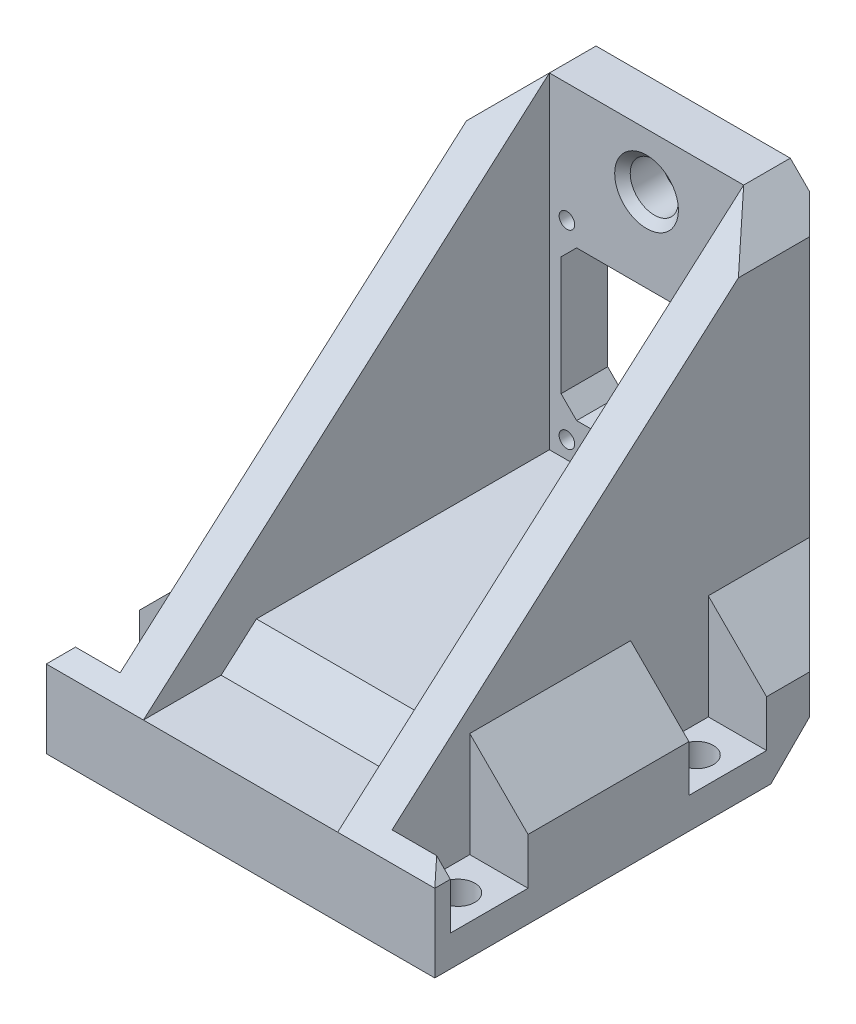
SolidWorks part; units mm, degrees
ref_plane "Front Plane" through (0, 0, 0) normal (0, 0, 1) x (1, 0, 0)
ref_plane "Top Plane" through (0, 0, 0) normal (0, 1, 0) x (1, 0, 0)
ref_plane "Right Plane" through (0, 0, 0) normal (1, 0, 0) x (0, 0, -1)
sketch "Sketch1" plane through (0, 0, 0) normal (0, 1, 0) x (1, 0, 0)
  line L1 (-25, 29.125) -> (25, 29.125)
  line L2 (-25, 29.125) -> (-25, -29.125)
  line L3 (-25, -29.125) -> (25, -29.125)
  line L4 (25, 29.125) -> (25, -29.125)
  line L5 (-25, 29.125) -> (25, -29.125) construction
  line L6 (-25, -29.125) -> (25, 29.125) construction
  point P0 (0, 0)
  dimension "D1" = 50
  dimension "D2" = 58.25
extrude "Boss-Extrude1" add sketch "Sketch1" along normal blind 10
sketch "Sketch2" plane through (0, 0, 0) normal (0, 1, 0) x (1, 0, 0)
  line L0 (-25, -29.125) -> (25, -29.125) construction
  line L1 (-21, -22.125) -> (21, -22.125) construction
  line L2 (-21, -22.125) -> (-21, 8.575) construction
  line L3 (-21, 8.575) -> (21, 8.575) construction
  line L4 (21, -22.125) -> (21, 8.575) construction
  line L5 (-21, -22.125) -> (21, 8.575) construction
  line L6 (-21, 8.575) -> (21, -22.125) construction
  circle A0 centre (-21, 8.575) radius 2.15
  circle A1 centre (-21, -22.125) radius 2.15
  circle A2 centre (21, 8.575) radius 2.15
  circle A3 centre (21, -22.125) radius 2.15
  point P0 (0, -6.775)
  dimension "D4" = 4.3
  dimension "D1" = 42
  dimension "D2" = 30.7
  dimension "D3" = 7
extrude "Cut-Extrude1" cut sketch "Sketch2" along normal blind 4
sketch "Sketch5" plane through (0, 10, 0) normal (0, 1, 0) x (1, 0, 0)
  line L0 (25, 29.125) -> (-25, 29.125) construction
  line L1 (-12.5, 23.125) -> (12.5, 23.125)
  line L2 (-12.5, 23.125) -> (-12.5, 29.125)
  line L3 (-12.5, 29.125) -> (12.5, 29.125)
  line L4 (12.5, 23.125) -> (12.5, 29.125)
  line L5 (-12.5, 23.125) -> (12.5, 29.125) construction
  line L6 (-12.5, 29.125) -> (12.5, 23.125) construction
  point P0 (0, 26.125)
  dimension "D1" = 6
  dimension "D2" = 25
extrude "Boss-Extrude3" add sketch "Sketch5" along normal blind 46
sketch "Sketch6" plane through (0, 0, -29.125) normal (0, 0, -1) x (-1, 0, 0)
  line L1 (-11, 19) -> (11, 19)
  line L2 (-11, 19) -> (-11, 38.25)
  line L3 (-11, 38.25) -> (11, 38.25)
  line L4 (11, 19) -> (11, 38.25)
  line L5 (-11, 19) -> (11, 38.25) construction
  line L6 (-11, 38.25) -> (11, 19) construction
  line L7 (-12.5, 56) -> (12.5, 56) construction
  point P0 (0, 28.625)
  dimension "D1" = 22
  dimension "D2" = 19.25
  dimension "D3" = 17.75
extrude "Cut-Extrude3" cut sketch "Sketch6" against normal up to next
sketch "Sketch7" plane through (0, 0, -23.125) normal (0, 0, 1) x (1, 0, 0)
  line L1 (-10.25, 16.25) -> (10.25, 16.25) construction
  line L2 (-10.25, 16.25) -> (-10.25, 40.7) construction
  line L3 (-10.25, 40.7) -> (10.25, 40.7) construction
  line L4 (10.25, 16.25) -> (10.25, 40.7) construction
  line L5 (-10.25, 16.25) -> (10.25, 40.7) construction
  line L6 (-10.25, 40.7) -> (10.25, 16.25) construction
  line L7 (-12.5, 56) -> (12.5, 56) construction
  circle A0 centre (10.25, 16.25) radius 1
  circle A1 centre (-10.25, 16.25) radius 1
  circle A2 centre (-10.25, 40.7) radius 1
  circle A3 centre (10.25, 40.7) radius 1
  point P0 (0, 28.475)
  dimension "D4" = 2
  dimension "D1" = 20.5
  dimension "D2" = 24.45
  dimension "D3" = 15.3
extrude "Cut-Extrude4" cut sketch "Sketch7" against normal blind 2.5
sketch "Sketch8" plane through (0, 0, -25.625) normal (0, 0, 1) x (1, 0, 0)
  circle A0 centre (-10.25, 40.7) radius 2
  circle A1 centre (10.25, 40.7) radius 2
  circle A2 centre (10.25, 16.25) radius 2
  circle A3 centre (-10.25, 16.25) radius 2
  dimension "D1" = 4
extrude "Cut-Extrude5" cut sketch "Sketch8" against normal up to next
sketch "Sketch9" plane through (12.5, 0, 0) normal (1, 0, 0) x (0, 0, -1)
  line L0 (29.125, 56) -> (23.125, 56)
  line L4 (-29.125, 10) -> (29.125, 10)
  line L5 (29.125, 10) -> (29.125, 56)
  line L6 (29.125, 56) -> (29.125, 10) construction
  line L8 (-29.125, 10) -> (23.125, 56)
extrude "Boss-Extrude4" add sketch "Sketch9" along normal blind 5
mirror "Mirror1" about plane through (0, 0, 0) normal (1, 0, 0) of "Boss-Extrude4"
chamfer "Chamfer1" distance 7.5 angle 45 2 edges at (17.5, 10, 0) (-17.5, 10, 0)
chamfer "Chamfer2" distance 10 angle 45 2 edges at (-25, 5, -29.125) (25, 5, -29.125)
chamfer "Chamfer4" distance 15 angle 45 1 edges at (0, 0, -29.125)
chamfer "Chamfer5" distance 5 angle 45 2 edges at (17.5, 56, -24.875) (-17.5, 56, -24.875)
chamfer "Chamfer7" distance 2 angle 45 4 edges at (-11, 38.25, -26.125) (-11, 19, -26.125) (11, 19, -26.125) (11, 38.25, -26.125)
sketch "Sketch10" plane through (0, 0, -29.125) normal (0, 0, -1) x (-1, 0, 0)
  circle A0 centre (0, 49) radius 3.1
  circle A1 centre (-10.25, 40.7) radius 2 construction
  dimension "D1" = 6.2
  dimension "D2" = 8.3
extrude "Cut-Extrude6" cut sketch "Sketch10" against normal up to next
chamfer "Chamfer8" distance 1 angle 45 2 edges at (-3.1, 49, -23.125) (-3.1, 49, -29.125)
sketch "Sketch11" plane through (-12.5, 0, 0) normal (1, 0, 0) x (0, 0, -1)
  line L0 (-19.125, 10) -> (23.125, 10)
  line L1 (23.125, 10) -> (23.125, 14)
  line L2 (23.125, 56) -> (23.125, 10) construction
  line L3 (23.125, 14) -> (-14.5815, 14)
  line L4 (29.125, 19) -> (23.125, 19) construction
  line L5 (-14.5815, 14) -> (-19.125, 10)
  line L7 (17.4457, 51) -> (-20.606, 17.5) construction
  line L9 (-29.125, 10) -> (19.125, 10) construction
  dimension "D1" = 5
  dimension "D2" = 10
extrude "Boss-Extrude5" add sketch "Sketch11" along normal up to next
sketch "Sketch17" plane through (17.5, 0, 0) normal (1, 0, 0) x (0, 0, -1)
  line L0 (-20.606, 17.5) -> (26.625, 17.5) construction
  line L1 (3.575, 4) -> (13.575, 4)
  line L2 (3.575, 4) -> (3.575, 17.5)
  line L3 (3.575, 17.5) -> (13.575, 17.5)
  line L4 (13.575, 4) -> (13.575, 17.5)
  line L5 (6.425, 4) -> (10.725, 4) construction
  line L6 (3.575, 17.5) -> (13.575, 4) construction
  line L7 (29.125, 53.5) -> (29.125, 15) construction
  point P8 (8.575, 10.75)
  dimension "D1" = 10
  dimension "D2" = 20.55
extrude "Cut-Extrude12" cut sketch "Sketch17" along normal up to next
pattern_linear "LPattern1" count 2 spacing 30.7 along (0, 0, 1) of "Cut-Extrude12"
mirror "Mirror3" about plane through (0, 0, 0) normal (1, 0, 0) of "LPattern1"
